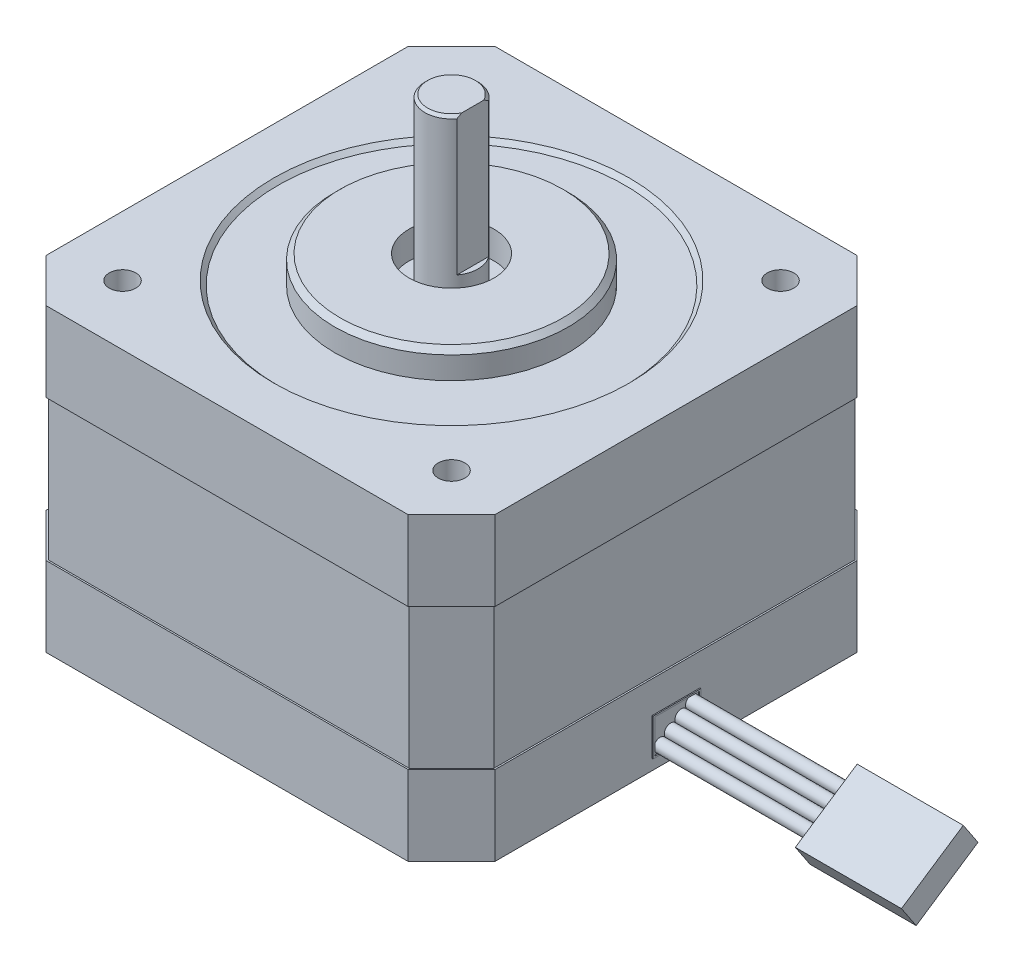
SolidWorks part; units mm, degrees
ref_plane "Alzado" through (0, 0, 0) normal (0, 0, 1) x (1, 0, 0)
ref_plane "Planta" through (0, 0, 0) normal (0, 1, 0) x (1, 0, 0)
ref_plane "Vista lateral" through (0, 0, 0) normal (1, 0, 0) x (0, 0, -1)
sketch "Croquis1" plane through (0, 0, 0) normal (0, 1, 0) x (1, 0, 0)
  line L0 (-21, 21) -> (21, -21) construction
  line L1 (-21, -21) -> (21, -21)
  line L2 (-21, -21) -> (-21, 21)
  line L3 (-21, 21) -> (21, 21)
  line L4 (21, -21) -> (21, 21)
  dimension "D1" = 42
extrude "Saliente-Extruir1" add sketch "Croquis1" along normal blind 28.3
chamfer "Chaflán1" distance 4 angle 45 4 edges at (21, 14.15, 21) (-21, 14.15, 21) (21, 14.15, -21) (-21, 14.15, -21)
sketch "Croquis3" plane through (0, 28.3, 0) normal (0, 1, 0) x (1, 0, 0)
  circle A0 centre (0, 0) radius 16.25
  dimension "D1" = 32.5
extrude "Cortar-Extruir1" cut sketch "Croquis3" against normal blind 0.4
ref_plane "Plano1" through (0, 30.5, 0) normal (0, 1, 0) x (1, 0, 0)
sketch "Croquis4" plane through (0, 30.5, 0) normal (0, 1, 0) x (1, 0, 0)
  circle A0 centre (0, 0) radius 11
  circle A1 centre (0, 0) radius 4
  dimension "D1" = 22
  dimension "D2" = 8
extrude "Saliente-Extruir2" add sketch "Croquis4" against normal up to next
chamfer "Chaflán2" distance 0.5 angle 45 2 edges at (0, 28.3, 16.25) (0, 30.5, 11)
sketch "Croquis5" plane through (0, 30.5, 0) normal (0, 1, 0) x (1, 0, 0)
  circle A0 centre (0, 0) radius 2.5
  dimension "D1" = 5
extrude "Saliente-Extruir3" add sketch "Croquis5" along normal blind 13 and the other way up to next separate body
sketch "Croquis6" plane through (0, 43.5, 0) normal (0, 1, 0) x (1, 0, 0)
  line L0 (2, 1.5) -> (2, -1.5)
  circle A0 centre (0, 0) radius 2.5 construction
  arc A1 (2, -1.5) -> (2, 1.5) centre (0, 0) ccw
  dimension "D1" = 4.5
extrude "Cortar-Extruir2" cut sketch "Croquis6" against normal up to surface (13 mm away) up to face at (0, 30.5, 10.5)
chamfer "Chaflán3" distance 0.25 angle 45 1 edges at (-2.5, 43.5, 0)
sketch "Croquis12" plane through (0, 28.3, 0) normal (0, 1, 0) x (1, 0, 0)
  line L0 (-17, 21) -> (-21, 17) construction
  line L1 (17, 21) -> (-17, 21) construction
  line L2 (-21, 17) -> (-21, -17) construction
  line L3 (-21, -17) -> (-17, -21) construction
  line L4 (-17, -21) -> (17, -21) construction
  line L5 (17, -21) -> (21, -17) construction
  line L6 (21, -17) -> (21, 17) construction
  line L7 (21, 17) -> (17, 21) construction
  line L8 (-17, 21) -> (-21, 17)
  line L9 (17, 21) -> (-17, 21)
  line L10 (-21, 17) -> (-21, -17)
  line L11 (-21, -17) -> (-17, -21)
  line L12 (-17, -21) -> (17, -21)
  line L13 (17, -21) -> (21, -17)
  line L14 (21, -17) -> (21, 17)
  line L15 (21, 17) -> (17, 21)
  line L16 (-17.0621, 21.15) -> (-21.15, 17.0621)
  line L17 (-21.15, 17.0621) -> (-21.15, -17.0621)
  line L18 (-21.15, -17.0621) -> (-17.0621, -21.15)
  line L19 (-17.0621, -21.15) -> (17.0621, -21.15)
  line L20 (17.0621, -21.15) -> (21.15, -17.0621)
  line L21 (21.15, -17.0621) -> (21.15, 17.0621)
  line L22 (21.15, 17.0621) -> (17.0621, 21.15)
  line L23 (17.0621, 21.15) -> (-17.0621, 21.15)
  dimension "D1" = 0.15
extrude "Saliente-Extruir9" add sketch "Croquis12" against normal blind 7.5
sketch "Croquis13" plane through (0, 0, 0) normal (0, -1, 0) x (1, 0, 0)
  line L0 (-17.0621, -21.15) -> (-21.15, -17.0621) construction
  line L1 (-17, -21) -> (-21, -17) construction
  line L2 (-21, -17) -> (-21, 17) construction
  line L3 (-21.15, -17.0621) -> (-21.15, 17.0621) construction
  line L4 (17, -21) -> (-17, -21) construction
  line L5 (17.0621, -21.15) -> (-17.0621, -21.15) construction
  line L6 (21.15, -17.0621) -> (17.0621, -21.15) construction
  line L7 (17, -21) -> (21, -17) construction
  line L8 (21, 17) -> (21, -17) construction
  line L9 (21.15, 17.0621) -> (21.15, -17.0621) construction
  line L10 (21, 17) -> (17, 21) construction
  line L11 (17.0621, 21.15) -> (21.15, 17.0621) construction
  line L12 (-17, 21) -> (17, 21) construction
  line L13 (-17.0621, 21.15) -> (17.0621, 21.15) construction
  line L14 (-21, 17) -> (-17, 21) construction
  line L15 (-21.15, 17.0621) -> (-17.0621, 21.15) construction
  line L16 (-17.0621, -21.15) -> (-21.15, -17.0621)
  line L17 (-17, -21) -> (-21, -17)
  line L18 (-21, -17) -> (-21, 17)
  line L19 (-21.15, -17.0621) -> (-21.15, 17.0621)
  line L20 (17, -21) -> (-17, -21)
  line L21 (17.0621, -21.15) -> (-17.0621, -21.15)
  line L22 (21.15, -17.0621) -> (17.0621, -21.15)
  line L23 (17, -21) -> (21, -17)
  line L24 (21, 17) -> (21, -17)
  line L25 (21.15, 17.0621) -> (21.15, -17.0621)
  line L26 (21, 17) -> (17, 21)
  line L27 (17.0621, 21.15) -> (21.15, 17.0621)
  line L28 (-17, 21) -> (17, 21)
  line L29 (-17.0621, 21.15) -> (17.0621, 21.15)
  line L30 (-21, 17) -> (-17, 21)
  line L31 (-21.15, 17.0621) -> (-17.0621, 21.15)
extrude "Saliente-Extruir10" add sketch "Croquis13" against normal blind 7.5
sketch "Croquis7" plane through (0, 28.3, 0) normal (0, 1, 0) x (1, 0, 0)
  line L0 (-15.5, 15.5) -> (15.5, -15.5) construction
  line L1 (-15.5, 15.5) -> (15.5, 15.5) construction
  line L2 (-15.5, 15.5) -> (-15.5, -15.5) construction
  line L3 (-15.5, -15.5) -> (15.5, -15.5) construction
  line L4 (15.5, 15.5) -> (15.5, -15.5) construction
  circle A0 centre (-15.5, 15.5) radius 1.25
  circle A1 centre (15.5, 15.5) radius 1.25
  circle A2 centre (15.5, -15.5) radius 1.25
  circle A3 centre (-15.5, -15.5) radius 1.25
  dimension "D1" = 2.5
  dimension "D2" = 31
extrude "Cortar-Extruir3" cut sketch "Croquis7" against normal blind 4.5
cosmetic thread "Rosca cosmética1" parameters "D1"=4.5, "D2"=3
cosmetic thread "Rosca cosmética2" parameters "D1"=4.5, "D2"=3
cosmetic thread "Rosca cosmética3" parameters "D1"=4.5, "D2"=3
cosmetic thread "Rosca cosmética4" parameters "D1"=4.5, "D2"=3
cosmetic thread "Rosca cosmética5" parameters "D1"=4.5, "D2"=3
cosmetic thread "Rosca cosmética6" parameters "D1"=4.5, "D2"=3
cosmetic thread "Rosca cosmética7" parameters "D1"=4.5, "D2"=3
sketch "Croquis8" plane through (-21.15, 0, 0) normal (-1, 0, 0) x (0, 0, 1)
  line L0 (0, 0) -> (0, 28.3) construction
  line L1 (-2.25, 4.5) -> (2.25, 4.5)
  line L2 (-2.25, 4.5) -> (-2.25, 1)
  line L3 (-2.25, 1) -> (2.25, 1)
  line L4 (2.25, 4.5) -> (2.25, 1)
  line L5 (-17, 0) -> (17, 0) construction
  line L6 (-17, 28.3) -> (17, 28.3) construction
  line L7 (-2, 4.25) -> (2, 4.25)
  line L8 (2, 4.25) -> (2, 1.25)
  line L9 (-2, 1.25) -> (2, 1.25)
  line L10 (-2, 4.25) -> (-2, 1.25)
  point P10 (0, 4.5)
  dimension "D1" = 3.5
  dimension "D2" = 4.5
  dimension "D3" = 1
  dimension "D4" = 0.25
extrude "Saliente-Extruir4" [suppressed] add sketch "Croquis8" along normal blind 0.1
sketch "Croquis9" [suppressed] plane through (-21, 0, 0) normal (-1, 0, 0) x (0, 0, 1)
  line L0 (-2, 4.25) -> (-2, 1.25) construction
  line L1 (2, 4.25) -> (-2, 4.25) construction
  line L4 (-1.431, 3.681) -> (1.431, 1.819) construction
  line L5 (2, 1.25) -> (2, 4.25) construction
  line L6 (-2, 1.25) -> (2, 1.25) construction
  circle A0 centre (-1.431, 3.681) radius 0.569
  circle A1 centre (1.431, 1.819) radius 0.569
  circle A2 centre (0.477, 2.4397) radius 0.569
  circle A3 centre (-0.477, 3.0603) radius 0.569
extrude "Saliente-Extruir6" [suppressed] add sketch "Croquis9" along normal blind 15 separate body contours A0 | A3 | A1 | A2 | L4 A3 | A2 L4
sketch "Croquis10" plane through (21.15, 0, 0) normal (1, 0, 0) x (0, 0, -1)
  line L0 (0, 28.3) -> (0, 0) construction
  line L1 (-2.25, 4.5) -> (2.25, 4.5)
  line L2 (-2.25, 4.5) -> (-2.25, 1)
  line L3 (-2.25, 1) -> (2.25, 1)
  line L4 (2.25, 4.5) -> (2.25, 1)
  line L5 (-17, 28.3) -> (17, 28.3) construction
  line L6 (-17, 0) -> (17, 0) construction
  line L7 (-2.1, 4.35) -> (-2.1, 1.15)
  line L8 (-2.1, 1.15) -> (2.1, 1.15)
  line L9 (2.1, 4.35) -> (2.1, 1.15)
  line L10 (-2.1, 4.35) -> (2.1, 4.35)
  point P10 (0, 4.5)
  dimension "D1" = 1
  dimension "D2" = 4.5
  dimension "D3" = 3.5
  dimension "D4" = 0.15
extrude "Saliente-Extruir7" add sketch "Croquis10" along normal blind 0.1
sketch "Croquis11" plane through (21, 0, 0) normal (1, 0, 0) x (0, 0, -1)
  line L1 (-2.1, 4.35) -> (-2.1, 1.15) construction
  line L3 (2.1, 1.15) -> (2.1, 4.35) construction
  line L4 (-1.4994, 1.7506) -> (1.4994, 3.7494) construction
  line L5 (-2.1, 1.15) -> (2.1, 1.15) construction
  line L6 (2.1, 4.35) -> (-2.1, 4.35) construction
  circle A0 centre (-1.4994, 1.7506) radius 0.6006
  circle A1 centre (-0.4998, 2.4169) radius 0.6006
  circle A2 centre (0.4998, 3.0831) radius 0.6006
  circle A3 centre (1.4994, 3.7494) radius 0.6006
extrude "Saliente-Extruir8" add sketch "Croquis11" along normal blind 15 separate body contours A0 | L4 A1 | A1 L4 | L4 A2 | A2 L4 | A3 region at (21, 2.629, 0.6412) region at (21, 1.9197, 0.9408) region at (21, 4.308, -1.3303) region at (21, 3.2952, -0.3584) region at (21, 2.871, -0.6412) region at (21, 2.2048, 0.3584)
sketch "Croquis14" plane through (36, 0, 0) normal (1, 0, 0) x (0, 0, -1)
  line L0 (-2.2191, -0.2313) -> (3.6056, 3.651)
  line L1 (3.6056, 3.651) -> (2.2191, 5.7313)
  line L2 (2.2191, 5.7313) -> (-3.6056, 1.849)
  line L3 (-3.6056, 1.849) -> (-2.2191, -0.2313)
  line L4 (-1.4994, 1.7506) -> (1.4994, 3.7494) construction
  line L5 (0.6933, 1.7099) -> (-0.6933, 3.7901) construction
  point P8 (0, 2.75)
  dimension "D1" = 2.5
  dimension "D2" = 7
extrude "Saliente-Extruir11" add sketch "Croquis14" along normal blind 10 separate body
